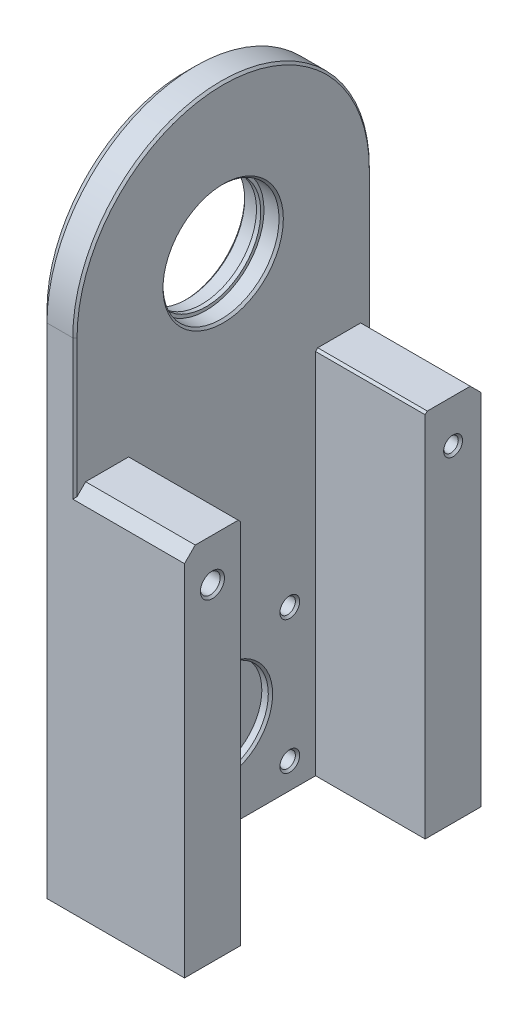
SolidWorks part; units mm, degrees
ref_plane "Ebene vorne" through (0, 0, 0) normal (0, 0, 1) x (1, 0, 0)
ref_plane "Ebene oben" through (0, 0, 0) normal (0, 1, 0) x (1, 0, 0)
ref_plane "Ebene rechts" through (0, 0, 0) normal (1, 0, 0) x (0, 0, -1)
sketch "Sketch2" plane through (0, 0, 0) normal (1, 0, 0) x (0, 0, -1)
  line L1 (0, 0) -> (69, 0)
  line L2 (0, 0) -> (0, 86)
  line L3 (0, 86) -> (69, 86)
  line L4 (69, 0) -> (69, 86)
  line L5 (0, 0) -> (69, 86) construction
  line L6 (0, 86) -> (69, 0) construction
  line L7 (0, 86) -> (69, 86)
  line L8 (0, 86) -> (0, 116)
  line L9 (0, 116) -> (69, 116)
  line L10 (69, 86) -> (69, 116)
  line L11 (0, 86) -> (69, 116) construction
  line L12 (0, 116) -> (69, 86) construction
  circle A0 centre (34.5, 116) radius 34.5
  circle A1 centre (34.5, 116) radius 12.75
  point P4 (34.5, 43)
  point P9 (34.5, 101)
  dimension "D4" = 69
  dimension "D5" = 25.5
  dimension "D1" = 69
  dimension "D2" = 86
  dimension "D3" = 30
extrude "Boss-Extrude1" add sketch "Sketch2" along normal blind 34.5 contours A0 L3 L2 L1 L4 | L7 A0 region at (0, 42.2679, -34.5) region at (0, 84.1895, -34.5)
sketch "Sketch3" plane through (34.5, 0, 0) normal (1, 0, 0) x (0, 0, -1)
  line L0 (13, 86) -> (13, 0)
  line L1 (0, 86) -> (69, 86) construction
  line L2 (0, 0) -> (69, 0) construction
  line L3 (13, 0) -> (56, 0)
  line L4 (56, 0) -> (56, 86)
  line L5 (56, 86) -> (13, 86)
  line L6 (0, 0) -> (0, 86) construction
  line L7 (69, 0) -> (69, 86) construction
  line L9 (13, 0) -> (56, 0)
  line L10 (13, 0) -> (13, 43)
  line L11 (13, 43) -> (56, 43)
  line L12 (56, 0) -> (56, 43)
  line L13 (13, 0) -> (56, 43) construction
  line L14 (13, 43) -> (56, 0) construction
  line L15 (56, 43) -> (13, 43)
  line L16 (56, 43) -> (56, 86)
  line L17 (56, 86) -> (13, 86)
  line L18 (13, 43) -> (13, 86)
  line L19 (56, 43) -> (13, 86) construction
  line L20 (56, 86) -> (13, 43) construction
  circle A0 centre (34.5, 21.5) radius 11
  circle A1 centre (34.5, 21.5) radius 5
  point P15 (34.5, 21.5)
  point P19 (34.5, 64.5)
  line M14 (69, 86) -> (0, 86)
  line M16 (0, 0) -> (69, 0)
  dimension "D3" = 22
  dimension "D4" = 10
  dimension "D1" = 13
  dimension "D2" = 13
extrude "Cut-Extrude1" cut sketch "Sketch3" against normal offset from surface (25.5 mm away) 9 contours L0 L11 L4 M14 | A0 A1 | A1 | L11 L0 L4 A0 M16 region at (34.5, 64.5, -34.5) region at (34.5, 42.3919, -34.5) region at (34.5, 21.5, -23.8111) region at (34.5, 21.5, -34.5) up to face at (0, 43, -34.5)
extrude "Boss-Extrude2" add sketch "Sketch2<3>" along normal up to surface (9 mm away) contours L9 A0 L7 | A0 L3 L10 | A0 L8 L3 | L9 A0 region at (0, 93.069, -4.894) region at (0, 93.069, -64.106) region at (0, 100.9752, -34.5) region at (0, 132.1024, -34.5) up to face at (9, 43, -34.5)
sketch "Sketch2<3>" plane through (0, 0, 0) normal (1, 0, 0) x (0, 0, -1) same geometry as "Sketch2"
extrude "Cut-Extrude2" cut sketch "Sketch3<3>" against normal offset from surface (27.5 mm away) 2 contours A0 A1 | A1 region at (34.5, 21.5, -23.8111) region at (34.5, 21.5, -34.5) up to face at (9, 76.3125, -34.5) offset beyond the face yes
sketch "Sketch3<3>" plane through (34.5, 0, 0) normal (1, 0, 0) x (0, 0, -1) same geometry as "Sketch3"
extrude "Cut-Extrude3" cut sketch "Sketch3<4>" against normal through all contours A1 region at (34.5, 21.5, -34.5)
sketch "Sketch3<4>" plane through (34.5, 0, 0) normal (1, 0, 0) x (0, 0, -1) same geometry as "Sketch3"
sketch "Sketch15" plane through (9, 0, 0) normal (1, 0, 0) x (0, 0, -1)
  circle A0 centre (34.5, 116) radius 13.5
  dimension "D1" = 27
extrude "Cut-Extrude4" cut sketch "Sketch15" against normal blind 4
ref_plane "Plane1" through (4.5, 0, 0) normal (1, 0, 0) x (0, 0, -1)
mirror "Mirror1" about plane through (4.5, 0, 0) normal (1, 0, 0) of "Cut-Extrude4"
hole_wizard "CBORE for M3 Hex Socket Head Cap Screw1" positions "Sketch4" profile "Sketch5" counterbore size "M3" standard "DIN" end condition through all
sketch "Sketch4" plane through (0, 0, 0) normal (-1, 0, 0) x (0, 0, 1)
  line L1 (-50, 6) -> (-19, 6)
  line L2 (-50, 6) -> (-50, 37)
  line L3 (-50, 37) -> (-19, 37)
  line L4 (-19, 6) -> (-19, 37)
  line L5 (-50, 6) -> (-19, 37) construction
  line L6 (-50, 37) -> (-19, 6) construction
  point P0 (-34.5, 21.5)
  point P1 (-19, 37)
  point P4 (-50, 6)
  point P5 (-50, 37)
  point P6 (-19, 6)
  dimension "D1" = 31
sketch "Sketch5" plane through (0, 6, -19) normal (0, 1, 0) x (0, 0, 1)
  line L0 (0, 0) -> (0, 34.5)
  line L1 (0, 34.5) -> (1.8, 34.5)
  line L3 (1.8, 34.5) -> (1.8, 3.4)
  line L4 (1.8, 3.4) -> (3.25, 3.4)
  line L5 (3.25, 3.4) -> (3.25, 0)
  line L7 (3.25, 0) -> (0, 0)
  line L11 (0, -6.35) -> (0, 107.95) construction
  dimension "Thru Hole Dia." = 3.6
  dimension "Thru Hole Depth" = 34.5
  dimension "C'Bore Dia." = 6.5
  dimension "C'Bore Depth" = 3.4
hole_wizard "Ø4.6 (4.6) Diameter Hole1" positions "Sketch8" profile "Sketch9" hole size "Ø4.6" standard "DIN"
sketch "Sketch8" plane through (0, 0, 0) normal (0, -1, 0) x (-1, 0, 0)
  line L0 (-34.5, 69) -> (-34.5, 0) construction
  line L1 (-34.5, 0) -> (0, 0) construction
  line L2 (-34.5, 0) -> (-34.5, 13) construction
  line L5 (-64.5, 6.5) -> (-4.5, 6.5)
  line L6 (-64.5, 6.5) -> (-64.5, 62.5)
  line L7 (-64.5, 62.5) -> (-4.5, 62.5)
  line L8 (-4.5, 6.5) -> (-4.5, 62.5)
  line L9 (-64.5, 6.5) -> (-4.5, 62.5) construction
  line L10 (-64.5, 62.5) -> (-4.5, 6.5) construction
  line L11 (-34.5, 69) -> (0, 69) construction
  line L12 (0, 0) -> (0, 69) construction
  point P9 (-34.5, 34.5)
  point P10 (-4.5, 62.5)
  point P15 (-4.5, 6.5)
  point P89 (-4.5, 34.5)
  dimension "D1" = 6.5
  dimension "D2" = 4.5
sketch "Sketch9" plane through (4.5, 0, -34.5) normal (1, 0, 0) x (0, 0, -1)
  line L0 (0, 0) -> (0, 7.382)
  line L1 (0, 7.382) -> (2.3, 6)
  line L2 (2.3, 6) -> (2.3, 0)
  line L5 (2.3, 0) -> (0, 0)
  line L10 (0, 7.382) -> (-2.3, 6) construction
  line L11 (0, -6.35) -> (0, 107.95) construction
  dimension "Hole Dia." = 4.6
  dimension "Hole Depth" = 6
  dimension "Drill Angle" = 118
hole_wizard "CBORE for M3 Hex Socket Head Cap Screw2" positions "Sketch10" profile "Sketch11" counterbore size "M3" standard "DIN" end condition through all
sketch "Sketch10" plane through (0, 0, 0) normal (-1, 0, 0) x (0, 0, 1)
  line L0 (-56, 86) -> (-69, 86) construction
  line L1 (-56, 86) -> (-69, 86)
  line L2 (-62.5, 86) -> (-62.5, 76) construction
  point P4 (-62.5, 76)
  dimension "D1" = 10
sketch "Sketch11" plane through (0, 76, -62.5) normal (0, 1, 0) x (0, 0, 1)
  line L0 (0, 0) -> (0, 34.5)
  line L1 (0, 34.5) -> (1.7, 34.5)
  line L3 (1.7, 34.5) -> (1.7, 3.4)
  line L4 (1.7, 3.4) -> (3.25, 3.4)
  line L5 (3.25, 3.4) -> (3.25, 0)
  line L7 (3.25, 0) -> (0, 0)
  line L11 (0, -6.35) -> (0, 107.95) construction
  dimension "Thru Hole Dia." = 3.4
  dimension "Thru Hole Depth" = 34.5
  dimension "C'Bore Dia." = 6.5
  dimension "C'Bore Depth" = 3.4
hole_wizard "Ø4.6 (4.6) Diameter Hole2" positions "Sketch12" profile "Sketch14" hole size "Ø4.6" standard "DIN"
sketch "Sketch12" plane through (34.5, 0, 0) normal (1, 0, 0) x (0, 0, -1)
  line L0 (6.5, 86) -> (6.5, 76) construction
  line L1 (0, 86) -> (13, 86) construction
  point P1 (6.5, 76)
  dimension "D1" = 10
sketch "Sketch14" plane through (34.5, 76, -6.5) normal (0, 1, 0) x (0, 0, -1)
  line L0 (0, 0) -> (0, 7.382)
  line L1 (0, 7.382) -> (2.3, 6)
  line L2 (2.3, 6) -> (2.3, 0)
  line L5 (2.3, 0) -> (0, 0)
  line L10 (0, 7.382) -> (-2.3, 6) construction
  line L11 (0, -6.35) -> (0, 107.95) construction
  dimension "Hole Dia." = 4.6
  dimension "Hole Depth" = 6
  dimension "Drill Angle" = 118
chamfer "2,5mm Chamfer1" distance 2.5 angle 45 5 edges at (21.75, 86, -69) (21.75, 86, 0) (0, 58, 0) (0, 150.5, -34.5) (0, 58, -69)
chamfer "0,5mm Chamfer2" distance 0.5 angle 45 24 edges at (0, 21.5, -39.5) (7, 21.5, -39.5) (9, 21.5, -45.5) (4.5, 0, -8.8) (4.5, 0, -36.8) (4.5, 0, -64.8) (9, 6, -20.8) (9, 6, -51.8) (9, 37, -51.8) (9, 37, -20.8) (34.5, 76, -60.8) (34.5, 76, -8.8) (9, 99.75, -69) (9, 99.75, 0) (9, 150.5, -34.5) (0, 6, -15.75) (0, 6, -46.75) (0, 37, -15.75) (0, 37, -46.75) (0, 76, -59.25) (21.75, 86, -56) (21.75, 86, -13) (0, 116, -48) (9, 116, -48)
